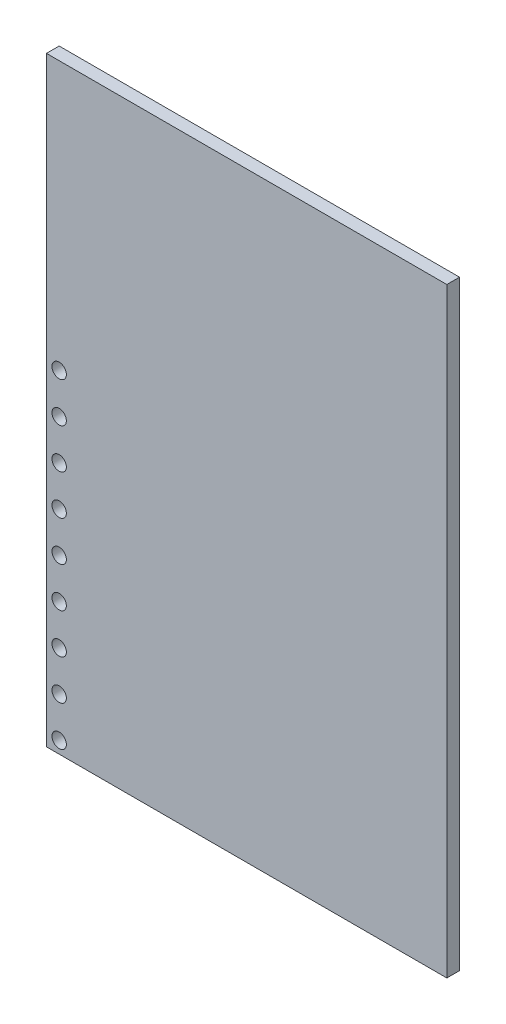
SolidWorks part; units mm, degrees
ref_plane "Front Plane" through (0, 0, 0) normal (0, 0, 1) x (1, 0, 0)
ref_plane "Top Plane" through (0, 0, 0) normal (0, 1, 0) x (1, 0, 0)
ref_plane "Right Plane" through (0, 0, 0) normal (1, 0, 0) x (0, 0, -1)
sketch "Sketch1" plane through (0, 0, 0) normal (0, 1, 0) x (1, 0, 0)
  line L1 (0, 0) -> (100, 0)
  line L2 (0, 0) -> (0, 3.175)
  line L3 (0, 3.175) -> (100, 3.175)
  line L4 (100, 0) -> (100, 3.175)
  dimension "D1" = 100
  dimension "D2" = 3.175
extrude "Boss-Extrude1" add sketch "Sketch1" along normal blind 150
sketch "Sketch2" plane through (0, 0, 0) normal (0, 0, 1) x (1, 0, 0)
  line L5 (0, 0) -> (6.35, 0)
  line L6 (0, 0) -> (0, 20)
  line L12 (0, 150) -> (0, 0) construction
  line L13 (0, 30) -> (0, 54)
  line L14 (0, 150) -> (0, 0) construction
  line L16 (0, 30) -> (0, 40)
  line L17 (0, 40) -> (0, 50)
  line L18 (0, 50) -> (0, 54)
  circle A4 centre (3.175, 3) radius 1.8
  circle A5 centre (3.175, 13) radius 1.8
  circle A6 centre (3.175, 23) radius 1.8
  circle A7 centre (3.175, 63) radius 1.8
  circle A8 centre (3.175, 43) radius 1.8
  circle A9 centre (3.175, 33) radius 1.8
  circle A10 centre (3.175, 83) radius 1.8
  circle A11 centre (3.175, 73) radius 1.8
  circle A12 centre (3.175, 53) radius 1.8
  point P1 (0, 0)
  point P9 (0, 0)
  point P10 (3.9708, 43.3293)
  point P15 (0, 0)
  point P23 (3.175, 78.5036)
  dimension "D5" = 10
  dimension "D6" = 3
  dimension "D7" = 10
  dimension "D3" = 10
  dimension "D4" = 3.6
  dimension "D1" = 10
  dimension "D2" = 10
  dimension "D8" = 3.175
  dimension "D9" = 10
  dimension "D10" = 10
  dimension "D11" = 10
extrude "Cut-Extrude2" cut sketch "Sketch2" against normal blind 5 contours A10
extrude "Cut-Extrude3" cut sketch "Sketch2<14>" against normal blind 5 contours A11
sketch "Sketch2<14>" plane through (0, 0, 0) normal (0, 0, 1) x (1, 0, 0) same geometry as "Sketch2"
extrude "Cut-Extrude4" cut sketch "Sketch2<15>" against normal blind 5 contours A12
sketch "Sketch2<15>" plane through (0, 0, 0) normal (0, 0, 1) x (1, 0, 0) same geometry as "Sketch2"
extrude "Cut-Extrude5" cut sketch "Sketch2<16>" against normal blind 5 contours A7
sketch "Sketch2<16>" plane through (0, 0, 0) normal (0, 0, 1) x (1, 0, 0) same geometry as "Sketch2"
extrude "Cut-Extrude6" cut sketch "Sketch2<17>" against normal blind 5 contours A8
sketch "Sketch2<17>" plane through (0, 0, 0) normal (0, 0, 1) x (1, 0, 0) same geometry as "Sketch2"
extrude "Cut-Extrude7" cut sketch "Sketch2<18>" against normal blind 5 contours A9
sketch "Sketch2<18>" plane through (0, 0, 0) normal (0, 0, 1) x (1, 0, 0) same geometry as "Sketch2"
extrude "Cut-Extrude8" cut sketch "Sketch2<19>" against normal blind 5 contours A6
sketch "Sketch2<19>" plane through (0, 0, 0) normal (0, 0, 1) x (1, 0, 0) same geometry as "Sketch2"
extrude "Cut-Extrude9" cut sketch "Sketch2<20>" against normal blind 5 contours A5
sketch "Sketch2<20>" plane through (0, 0, 0) normal (0, 0, 1) x (1, 0, 0) same geometry as "Sketch2"
extrude "Cut-Extrude10" cut sketch "Sketch2<21>" against normal blind 5 contours A4
sketch "Sketch2<21>" plane through (0, 0, 0) normal (0, 0, 1) x (1, 0, 0) same geometry as "Sketch2"
